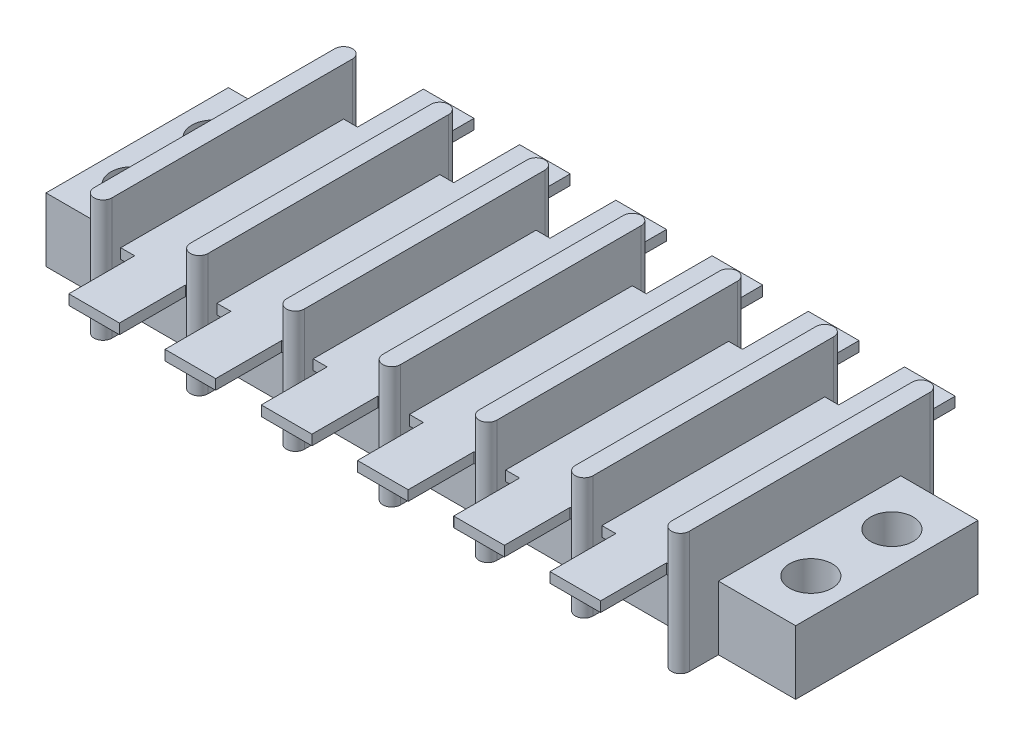
SolidWorks part; units mm, degrees
ref_plane "Front Plane" through (0, 0, 0) normal (0, 0, 1) x (1, 0, 0)
ref_plane "Top Plane" through (0, 0, 0) normal (0, 1, 0) x (1, 0, 0)
ref_plane "Right Plane" through (0, 0, 0) normal (1, 0, 0) x (0, 0, -1)
sketch "Sketch1" plane through (0, 0, 0) normal (0, 1, 0) x (1, 0, 0)
  line L1 (-37, -9) -> (37, -9)
  line L2 (-37, -9) -> (-37, 9)
  line L3 (-37, 9) -> (37, 9)
  line L4 (37, -9) -> (37, 9)
  line L5 (-37, -9) -> (37, 9) construction
  line L6 (-37, 9) -> (37, -9) construction
  point P0 (0, 0)
  dimension "D1" = 74
  dimension "D2" = 18
extrude "Boss-Extrude1" add sketch "Sketch1" along normal blind 6.3
sketch "Sketch4" plane through (0, 0, 0) normal (0, 1, 0) x (1, 0, 0)
  line L0 (-28.5, 11.875) -> (-28.5, -11.875) construction
  line L1 (-27.625, 11.875) -> (-27.625, -11.875)
  line L2 (-29.375, 11.875) -> (-29.375, -11.875)
  line L3 (-37, 9) -> (-37, -9) construction
  line L4 (-19, 11.875) -> (-19, -11.875) construction
  line L7 (-18.125, 11.875) -> (-18.125, -11.875)
  line L10 (-19.875, 11.875) -> (-19.875, -11.875)
  line L13 (-9.5, 11.875) -> (-9.5, -11.875) construction
  line L16 (-8.625, 11.875) -> (-8.625, -11.875)
  line L19 (-10.375, 11.875) -> (-10.375, -11.875)
  line L22 (0, 11.875) -> (0, -11.875) construction
  line L23 (0.875, 11.875) -> (0.875, -11.875)
  line L24 (-0.875, 11.875) -> (-0.875, -11.875)
  line L25 (9.5, 11.875) -> (9.5, -11.875) construction
  line L26 (10.375, 11.875) -> (10.375, -11.875)
  line L27 (8.625, 11.875) -> (8.625, -11.875)
  line L28 (19, 11.875) -> (19, -11.875) construction
  line L29 (19.875, 11.875) -> (19.875, -11.875)
  line L30 (18.125, 11.875) -> (18.125, -11.875)
  line L31 (28.5, 11.875) -> (28.5, -11.875) construction
  line L32 (29.375, 11.875) -> (29.375, -11.875)
  line L33 (27.625, 11.875) -> (27.625, -11.875)
  arc A0 (-27.625, 11.875) -> (-29.375, 11.875) centre (-28.5, 11.875) ccw
  arc A1 (-29.375, -11.875) -> (-27.625, -11.875) centre (-28.5, -11.875) ccw
  arc A14 (-18.125, 11.875) -> (-19.875, 11.875) centre (-19, 11.875) ccw
  arc A15 (-19.875, -11.875) -> (-18.125, -11.875) centre (-19, -11.875) ccw
  arc A16 (-8.625, 11.875) -> (-10.375, 11.875) centre (-9.5, 11.875) ccw
  arc A17 (-10.375, -11.875) -> (-8.625, -11.875) centre (-9.5, -11.875) ccw
  arc A18 (0.875, 11.875) -> (-0.875, 11.875) centre (0, 11.875) ccw
  arc A19 (-0.875, -11.875) -> (0.875, -11.875) centre (0, -11.875) ccw
  arc A20 (10.375, 11.875) -> (8.625, 11.875) centre (9.5, 11.875) ccw
  arc A21 (8.625, -11.875) -> (10.375, -11.875) centre (9.5, -11.875) ccw
  arc A22 (19.875, 11.875) -> (18.125, 11.875) centre (19, 11.875) ccw
  arc A23 (18.125, -11.875) -> (19.875, -11.875) centre (19, -11.875) ccw
  arc A24 (29.375, 11.875) -> (27.625, 11.875) centre (28.5, 11.875) ccw
  arc A25 (27.625, -11.875) -> (29.375, -11.875) centre (28.5, -11.875) ccw
  point P2 (-28.5, 0)
  point P7 (0, 0)
  point P10 (-37, 0)
  point P11 (-28.5, 11)
  point P12 (-28.5, -11)
  point P15 (-19, 0)
  point P20 (-19, 11)
  point P21 (-19, -11)
  point P22 (0, 0)
  point P25 (-9.5, 0)
  point P30 (-9.5, 11)
  point P31 (-9.5, -11)
  point P34 (0, 0)
  point P39 (0, 11)
  point P40 (0, -11)
  point P41 (0, 0)
  point P44 (9.5, 0)
  point P49 (9.5, 11)
  point P50 (9.5, -11)
  point P53 (19, 0)
  point P58 (19, 11)
  point P59 (19, -11)
  point P62 (28.5, 0)
  point P67 (0, 0)
  point P68 (28.5, 11)
  point P69 (28.5, -11)
  point P70 (0, 0)
  dimension "D1" = 22
  dimension "D2" = 1.75
  dimension "D3" = 22
  dimension "D4" = 1.75
  dimension "D5" = 22
  dimension "D6" = 1.75
  dimension "D7" = 22
  dimension "D8" = 1.75
  dimension "D9" = 22
  dimension "D10" = 1.75
  dimension "D11" = 22
  dimension "D12" = 1.75
  dimension "D13" = 22
  dimension "D14" = 1.75
  dimension "D15" = 8.5
  dimension "D16" = 9.5
  dimension "D17" = 9.5
  dimension "D18" = 9.5
  dimension "D19" = 9.5
  dimension "D20" = 9.5
  dimension "D21" = 9.5
extrude "Boss-Extrude2" add sketch "Sketch4" along normal blind 12
sketch "Sketch5" plane through (0, 6.3, 0) normal (0, 1, 0) x (1, 0, 0)
  line L0 (-37, 9) -> (-37, -9) construction
  line L1 (-27.625, 11) -> (-26.25, 11)
  line L2 (-27.625, 11) -> (-27.625, -11)
  line L3 (-27.625, -11) -> (-26.25, -11)
  line L4 (-19.875, 11) -> (-19.875, -11)
  line L5 (-27.625, 11) -> (-19.875, -11) construction
  line L6 (-27.625, -11) -> (-19.875, 11) construction
  line L7 (-27.625, -11.875) -> (-27.625, 11.875) construction
  line L8 (-21.25, 11) -> (-19.875, 11)
  line L9 (-26.25, 17.5) -> (-21.25, 17.5)
  line L10 (-26.25, 17.5) -> (-26.25, 11)
  line L11 (-26.25, -17.5) -> (-21.25, -17.5)
  line L12 (-21.25, 17.5) -> (-21.25, 11)
  line L13 (-26.25, 17.5) -> (-21.25, -17.5) construction
  line L14 (-26.25, -17.5) -> (-21.25, 17.5) construction
  line L15 (-26.25, -11) -> (-26.25, -17.5)
  line L16 (-21.25, -11) -> (-21.25, -17.5)
  line L17 (-21.25, -11) -> (-19.875, -11)
  line L18 (-18.125, 11) -> (-16.75, 11)
  line L19 (-18.125, 11) -> (-18.125, -11)
  line L20 (-18.125, -11) -> (-16.75, -11)
  line L21 (-10.375, 11) -> (-10.375, -11)
  line L22 (-18.125, 11) -> (-10.375, -11) construction
  line L23 (-18.125, -11) -> (-10.375, 11) construction
  line L24 (-11.75, 11) -> (-10.375, 11)
  line L25 (-16.75, 17.5) -> (-11.75, 17.5)
  line L26 (-16.75, 17.5) -> (-16.75, 11)
  line L27 (-16.75, -17.5) -> (-11.75, -17.5)
  line L28 (-11.75, 17.5) -> (-11.75, 11)
  line L29 (-16.75, 17.5) -> (-11.75, -17.5) construction
  line L30 (-16.75, -17.5) -> (-11.75, 17.5) construction
  line L31 (-16.75, -11) -> (-16.75, -17.5)
  line L32 (-11.75, -11) -> (-11.75, -17.5)
  line L33 (-11.75, -11) -> (-10.375, -11)
  line L34 (-18.125, -11.875) -> (-18.125, 11.875) construction
  line L35 (-8.625, 11) -> (-7.25, 11)
  line L36 (-8.625, 11) -> (-8.625, -11)
  line L37 (-8.625, -11) -> (-7.25, -11)
  line L38 (-0.875, 11) -> (-0.875, -11)
  line L39 (-8.625, 11) -> (-0.875, -11) construction
  line L40 (-8.625, -11) -> (-0.875, 11) construction
  line L41 (-2.25, 11) -> (-0.875, 11)
  line L42 (-7.25, 17.5) -> (-2.25, 17.5)
  line L43 (-7.25, 17.5) -> (-7.25, 11)
  line L44 (-7.25, -17.5) -> (-2.25, -17.5)
  line L45 (-2.25, 17.5) -> (-2.25, 11)
  line L46 (-7.25, 17.5) -> (-2.25, -17.5) construction
  line L47 (-7.25, -17.5) -> (-2.25, 17.5) construction
  line L48 (-7.25, -11) -> (-7.25, -17.5)
  line L49 (-2.25, -11) -> (-2.25, -17.5)
  line L50 (-2.25, -11) -> (-0.875, -11)
  line L51 (-10.375, 11.875) -> (-10.375, -11.875) construction
  line L52 (-8.625, -11.875) -> (-8.625, 11.875) construction
  line L53 (-0.875, 11.875) -> (-0.875, -11.875) construction
  line L54 (0.875, 11) -> (2.25, 11)
  line L55 (0.875, 11) -> (0.875, -11)
  line L56 (0.875, -11) -> (2.25, -11)
  line L57 (8.625, 11) -> (8.625, -11)
  line L58 (0.875, 11) -> (8.625, -11) construction
  line L59 (0.875, -11) -> (8.625, 11) construction
  line L60 (7.25, 11) -> (8.625, 11)
  line L61 (2.25, 17.5) -> (7.25, 17.5)
  line L62 (2.25, 17.5) -> (2.25, 11)
  line L63 (2.25, -17.5) -> (7.25, -17.5)
  line L64 (7.25, 17.5) -> (7.25, 11)
  line L65 (2.25, 17.5) -> (7.25, -17.5) construction
  line L66 (2.25, -17.5) -> (7.25, 17.5) construction
  line L67 (2.25, -11) -> (2.25, -17.5)
  line L68 (7.25, -11) -> (7.25, -17.5)
  line L69 (7.25, -11) -> (8.625, -11)
  line L70 (10.375, 11) -> (11.75, 11)
  line L71 (10.375, 11) -> (10.375, -11)
  line L72 (10.375, -11) -> (11.75, -11)
  line L73 (18.125, 11) -> (18.125, -11)
  line L74 (10.375, 11) -> (18.125, -11) construction
  line L75 (10.375, -11) -> (18.125, 11) construction
  line L76 (16.75, 11) -> (18.125, 11)
  line L77 (11.75, 17.5) -> (16.75, 17.5)
  line L78 (11.75, 17.5) -> (11.75, 11)
  line L79 (11.75, -17.5) -> (16.75, -17.5)
  line L80 (16.75, 17.5) -> (16.75, 11)
  line L81 (11.75, 17.5) -> (16.75, -17.5) construction
  line L82 (11.75, -17.5) -> (16.75, 17.5) construction
  line L83 (11.75, -11) -> (11.75, -17.5)
  line L84 (16.75, -11) -> (16.75, -17.5)
  line L85 (16.75, -11) -> (18.125, -11)
  line L86 (19.875, 11) -> (21.25, 11)
  line L87 (19.875, 11) -> (19.875, -11)
  line L88 (19.875, -11) -> (21.25, -11)
  line L89 (27.625, 11) -> (27.625, -11)
  line L90 (19.875, 11) -> (27.625, -11) construction
  line L91 (19.875, -11) -> (27.625, 11) construction
  line L92 (26.25, 11) -> (27.625, 11)
  line L93 (21.25, 17.5) -> (26.25, 17.5)
  line L94 (21.25, 17.5) -> (21.25, 11)
  line L95 (21.25, -17.5) -> (26.25, -17.5)
  line L96 (26.25, 17.5) -> (26.25, 11)
  line L97 (21.25, 17.5) -> (26.25, -17.5) construction
  line L98 (21.25, -17.5) -> (26.25, 17.5) construction
  line L99 (21.25, -11) -> (21.25, -17.5)
  line L100 (26.25, -11) -> (26.25, -17.5)
  line L101 (26.25, -11) -> (27.625, -11)
  line L102 (0.875, -9) -> (0.875, 9) construction
  line L103 (10.375, -9) -> (10.375, 9) construction
  line L104 (19.875, -9) -> (19.875, 9) construction
  line L105 (18.125, 11.875) -> (18.125, -11.875) construction
  line L106 (27.625, 11.875) -> (27.625, -11.875) construction
  point P0 (-23.75, 0)
  point P5 (-14.25, 0)
  point P8 (-37, 0)
  point P11 (-23.75, 0)
  point P26 (-14.25, 0)
  point P37 (0, 0)
  point P40 (-4.75, 0)
  point P45 (-4.75, 0)
  point P56 (0, 0)
  point P63 (0, 0)
  point P64 (4.75, 0)
  point P69 (14.25, 0)
  point P70 (4.75, 0)
  point P85 (14.25, 0)
  point P96 (23.75, 0)
  point P101 (23.75, 0)
  point P112 (0, 0)
  point P113 (0, 0)
  dimension "D1" = 7.75
  dimension "D2" = 22
  dimension "D3" = 5
  dimension "D4" = 35
  dimension "D5" = 22
  dimension "D6" = 5
  dimension "D7" = 35
  dimension "D8" = 22
  dimension "D9" = 5
  dimension "D10" = 35
  dimension "D11" = 7.75
  dimension "D12" = 22
  dimension "D13" = 5
  dimension "D14" = 35
  dimension "D15" = 22
  dimension "D16" = 5
  dimension "D17" = 35
  dimension "D18" = 22
  dimension "D19" = 5
  dimension "D20" = 35
extrude "Boss-Extrude3" add sketch "Sketch5" along normal blind 1
sketch "Sketch6" plane through (0, 6.3, 0) normal (0, 1, 0) x (1, 0, 0)
  line L0 (-29.375, 9) -> (-37, 9) construction
  line L1 (-37, -9) -> (-29.375, -9) construction
  line L2 (-37, 9) -> (-37, -9) construction
  line L3 (37, -9) -> (37, 9) construction
  circle A0 centre (-33.5, 4) radius 2.1
  circle A1 centre (-33.5, -4) radius 2.1
  circle A2 centre (33.5, 4) radius 2.1
  circle A3 centre (33.5, -4) radius 2.1
  point P8 (0, 0)
  point P9 (0, 0)
  point P10 (0, 0)
  point P11 (0, 0)
  point P12 (0, 0)
  dimension "D1" = 4.2
  dimension "D2" = 4.2
  dimension "D3" = 4.2
  dimension "D4" = 4.2
  dimension "D5" = 5
  dimension "D6" = 5
  dimension "D7" = 3.5
  dimension "D8" = 3.5
extrude "Cut-Extrude1" cut sketch "Sketch6" against normal through all
